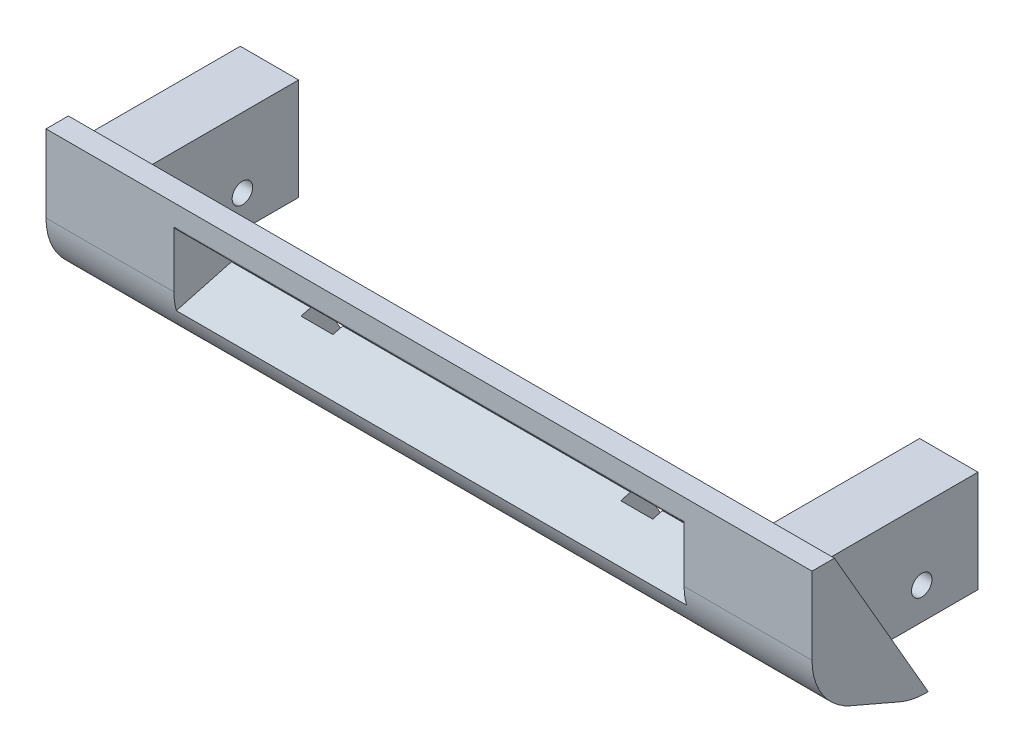
SolidWorks part; units mm, degrees
ref_plane "Front Plane" through (0, 0, 0) normal (0, 0, 1) x (1, 0, 0)
ref_plane "Top Plane" through (0, 0, 0) normal (0, 1, 0) x (1, 0, 0)
ref_plane "Right Plane" through (0, 0, 0) normal (1, 0, 0) x (0, 0, -1)
sketch "Sketch1" plane through (0, 0, 0) normal (1, 0, 0) x (0, 0, -1)
  line L0 (0, 0) -> (-29.3294, 50.8)
  line L1 (0, 0) -> (50, 0) construction
  line L2 (-29.3294, 50.8) -> (-36.3294, 50.8)
  line L3 (-36.3294, 13.503) -> (-5, 0)
  line L6 (-36.3294, 50.8) -> (-36.3294, 13.503)
  line L7 (-5, 0) -> (0, 0)
  point P5 (-87.9825, 36.4141)
  point P9 (-36.3294, 29.766)
  point P10 (-36.3294, 17.4717)
  point P11 (-7.5578, 0)
  point P12 (0, 0)
  point P13 (0, 0)
  point P14 (-36.3294, 17.3687)
  point P15 (-36.3294, 18.4754)
  point P16 (-36.3294, 13.9682)
  point P17 (0, 0)
  point P18 (-4.4936, 0)
  dimension "D1" = 5
  dimension "D2" = 60
  dimension "D3" = 37.297
extrude "Boss-Extrude2" add sketch "Sketch1" along normal mid plane 239.55
sketch "Sketch2" plane through (0, 0, 0) normal (0, 0, 1) x (1, 0, 0)
  line L0 (0, 0) -> (0, 50.8) construction
  line L5 (115.75, 47.625) -> (96.7, 47.625) construction
  line L6 (115.75, 47.625) -> (115.75, 15) construction
  line L11 (115.75, 15) -> (96.7, 15) construction
  line L12 (96.7, 47.625) -> (96.7, 15) construction
  line L13 (119.775, 0) -> (-119.775, 0) construction
  line L14 (115.35, 47.225) -> (115.35, 15.4)
  line L15 (115.35, 15.4) -> (97.1, 15.4)
  line L28 (97.1, 47.225) -> (97.1, 15.4)
  line L29 (115.35, 47.225) -> (97.1, 47.225)
  line L30 (-96.7, 47.625) -> (-96.7, 15) construction
  line L31 (-115.75, 15) -> (-96.7, 15) construction
  line L32 (-115.75, 47.625) -> (-115.75, 15) construction
  line L33 (-115.75, 47.625) -> (-96.7, 47.625) construction
  line L34 (-115.35, 47.225) -> (-97.1, 47.225)
  line L35 (-97.1, 47.225) -> (-97.1, 15.4)
  line L36 (-115.35, 15.4) -> (-97.1, 15.4)
  line L37 (-115.35, 47.225) -> (-115.35, 15.4)
  line L40 (119.775, 50.8) -> (-119.775, 50.8) construction
  line L41 (119.775, 0) -> (119.775, 50.8) construction
  dimension "D2" = 19.05
  dimension "D4" = 3.175
  dimension "D7" = 4.025
  dimension "D1" = 193.4
  dimension "D3" = 15
  dimension "D5" = 0.4
extrude "Boss-Extrude1" add sketch "Sketch2" along normal up to surface and the other way blind 20 up to face at (0, 25.4, 14.6647)
sketch "Sketch12" plane through (0, -1.8174, 0.7833) normal (0, -0.9183, 0.3958) x (1, 0, 0)
  line L0 (-95.2, -611.0491) -> (-95.2, 0.926) construction
  line L1 (-95.2, -611.0491) -> (-95.2, 0.926) construction
  line L2 (119.775, 0) -> (-119.775, 0) construction
  line L3 (70, 15) -> (-70, 15)
  line L4 (70, 15) -> (70, 0)
  line L5 (70, 0) -> (-70, 0)
  line L6 (-70, 15) -> (-70, 0)
  line L7 (70, 15) -> (-70, 0) construction
  line L8 (70, 0) -> (-70, 15) construction
  line L10 (95.2, 43.4693) -> (-95.2, 43.4693)
  line L11 (95.2, 43.4693) -> (95.2, 18.4693)
  line L12 (95.2, 18.4693) -> (-95.2, 18.4693)
  line L13 (-95.2, 43.4693) -> (-95.2, 18.4693)
  line L14 (95.2, 43.4693) -> (-95.2, 18.4693) construction
  line L15 (95.2, 18.4693) -> (-95.2, 43.4693) construction
  line L16 (-120.6, 53.4693) -> (120.6, 53.4693) construction
  point P2 (0, 7.5)
  point P11 (0, 30.9693)
  dimension "D1" = 15
  dimension "D2" = 140
  dimension "D3" = 10
  dimension "D4" = 25
  dimension "D5" = 3.4693
extrude "Cut-Extrude4" [suppressed] cut sketch "Sketch12" against normal up to next
hole_wizard "M6 Clearance Hole1" positions "Sketch11" profile "Sketch10" hole size "M6" standard "ANSI Metric" end condition through all
sketch "Sketch11" plane through (115.35, 0, 0) normal (1, 0, 0) x (0, 0, -1)
  point P0 (2.4206, 25.4)
sketch "Sketch10" plane through (115.35, 25.4, -2.4206) normal (0, 1, 0) x (0, 0, -1)
  line L0 (0, 0) -> (0, 235.125)
  line L1 (0, 235.125) -> (3.2, 235.125)
  line L2 (3.2, 235.125) -> (3.2, 0)
  line L5 (3.2, 0) -> (0, 0)
  line L11 (0, -6.35) -> (0, 107.95) construction
  dimension "Thru Hole Dia." = 6.4
  dimension "Thru Hole Depth" = 235.125
sketch "Sketch13" plane through (0, 0, 0) normal (0, 0, 1) x (1, 0, 0)
  line L0 (119.775, 0) -> (-119.775, 0) construction
  line L1 (-76.872, 13.5) -> (76.872, 13.5)
  line L2 (-76.872, 13.5) -> (-76.872, 0)
  line L3 (-76.872, 0) -> (76.872, 0)
  line L4 (76.872, 13.5) -> (76.872, 0)
  line L5 (-76.872, 13.5) -> (76.872, 0) construction
  line L6 (-76.872, 0) -> (76.872, 13.5) construction
  line L7 (119.775, 50.8) -> (-119.775, 50.8) construction
  line L8 (-79.775, 25.8) -> (79.775, 25.8)
  line L9 (-79.775, 25.8) -> (-79.775, 40.8)
  line L10 (-79.775, 40.8) -> (79.775, 40.8)
  line L11 (79.775, 25.8) -> (79.775, 40.8)
  line L12 (-79.775, 25.8) -> (79.775, 40.8) construction
  line L13 (-79.775, 40.8) -> (79.775, 25.8) construction
  line L14 (-119.775, 50.8) -> (-119.775, 13.503) construction
  line L15 (0, 50.8) -> (0, -69.7748) construction
  point P0 (0, 6.75)
  point P7 (0, 33.3)
  point P16 (0, 0)
  dimension "D1" = 13.5
  dimension "D2" = 10
  dimension "D3" = 40
  dimension "D4" = 15
extrude "Cut-Extrude6" cut sketch "Sketch13" against normal through all both and the other way through all
chamfer "Chamfer5" distance 18 angle 15 1 edges at (0, 40.8, 23.5559) first distance on face at (0, 40.8, 29.9426)
chamfer "Chamfer6" distance 18 angle 15 1 edges at (0, 25.8, 36.3294) first distance on face at (0, 25.8, 25.6125)
sketch "Sketch14" plane through (0, 13.5, 0) normal (0, -1, 0) x (1, 0, 0)
  line L0 (-49.8748, 11.7942) -> (50.6947, 11.7942) construction
  line L1 (76.872, 7.7942) -> (-76.872, 7.7942) construction
  line L2 (47.1947, 15.7942) -> (54.1947, 15.7942)
  line L3 (47.1947, 15.7942) -> (47.1947, 7.7942)
  line L4 (47.1947, 7.7942) -> (54.1947, 7.7942)
  line L5 (54.1947, 15.7942) -> (54.1947, 7.7942)
  line L6 (47.1947, 15.7942) -> (54.1947, 7.7942) construction
  line L7 (47.1947, 7.7942) -> (54.1947, 15.7942) construction
  line L9 (-53.3748, 15.7942) -> (-46.3748, 15.7942)
  line L10 (-53.3748, 15.7942) -> (-53.3748, 7.7942)
  line L11 (-53.3748, 7.7942) -> (-46.3748, 7.7942)
  line L12 (-46.3748, 15.7942) -> (-46.3748, 7.7942)
  line L13 (-53.3748, 15.7942) -> (-46.3748, 7.7942) construction
  line L14 (-53.3748, 7.7942) -> (-46.3748, 15.7942) construction
  point P0 (50.6947, 11.7942)
  point P3 (0.4099, 11.7942)
  dimension "D1" = 7
  dimension "D2" = 7
  dimension "D3" = 8
ref_plane "Plane2" through (0, 13.5, 7.7942) normal (0, 0.866, 0.5) x (-1, 0, 0)
sketch "Sketch15" plane through (0, 13.5, 7.7942) normal (0, 0.866, 0.5) x (-1, 0, 0)
  line L0 (-50, 3) -> (50, 3) construction
  line L1 (-76.872, 0) -> (76.872, 0) construction
  line L2 (-45, 6) -> (-55, 6)
  line L3 (-45, 6) -> (-45, 0)
  line L4 (-45, 0) -> (-55, 0)
  line L5 (-55, 6) -> (-55, 0)
  line L6 (-45, 6) -> (-55, 0) construction
  line L7 (-45, 0) -> (-55, 6) construction
  line L9 (45, 6) -> (55, 6)
  line L10 (45, 6) -> (45, 0)
  line L11 (45, 0) -> (55, 0)
  line L12 (55, 6) -> (55, 0)
  line L13 (45, 6) -> (55, 0) construction
  line L14 (45, 0) -> (55, 6) construction
  point P3 (0, 3)
  dimension "D1" = 10
  dimension "D2" = 10
  dimension "D3" = 6
  dimension "D4" = 100
extrude "Cut-Extrude8" cut sketch "Sketch15" along normal up to surface (16.7306 mm away) up to face at (0, 23.3885, 27.3294)
fillet "Fillet1" radius 4 1 edges at (0, 42.2004, 36.3294) second distance 1 first distance on face at (0, 43.5887, 31.1484)
fillet "Fillet2" radius 20 2 edges at (-98.3235, 0, 5) (98.3235, 0, 5)
fillet "Fillet3" radius 20 1 edges at (0, 13.503, 36.3294)
equation "\"D1@Sketch2\"=187.05mm+0.25in"
equation "\"RailSpacing\"= 188.75mm"
equation "\"D1@Boss-Extrude2\"=\"RailSpacing\"+2in"
